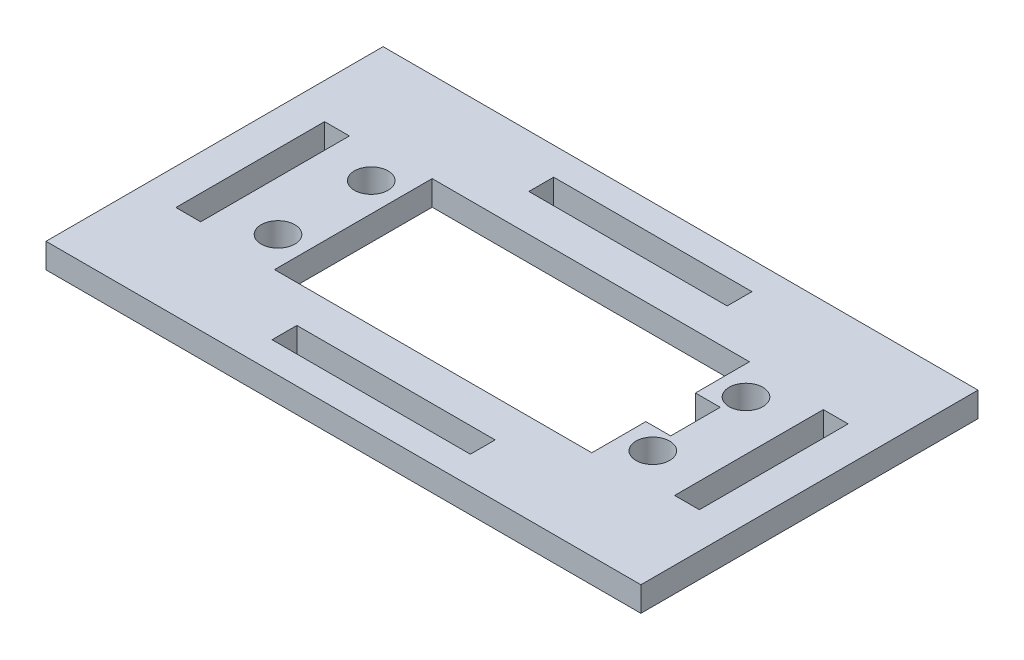
SolidWorks part; units mm, degrees
ref_plane "Front" through (0, 0, 0) normal (0, 0, 1) x (1, 0, 0)
ref_plane "Top" through (0, 0, 0) normal (0, 1, 0) x (1, 0, 0)
ref_plane "Right" through (0, 0, 0) normal (1, 0, 0) x (0, 0, -1)
sketch "Sketch1" plane through (0, 0, 0) normal (0, 1, 0) x (1, 0, 0)
  line L0 (0, 10.0965) -> (40.64, 10.0965) construction
  line L1 (0, 0) -> (40.64, 0)
  line L2 (0, 0) -> (0, 20.193)
  line L3 (0, 20.193) -> (40.64, 20.193)
  line L4 (40.64, 0) -> (40.64, 20.193)
  line L5 (-17.78, -11.4935) -> (58.42, -11.4935)
  line L6 (-17.78, -11.4935) -> (-17.78, 31.6865)
  line L7 (-17.78, 31.6865) -> (58.42, 31.6865)
  line L8 (58.42, -11.4935) -> (58.42, 31.6865)
  line L9 (44.323, 16.0655) -> (44.323, 4.1275) construction
  line L10 (20.32, 20.193) -> (20.32, 0) construction
  line L11 (7.62, -7.9375) -> (33.02, -7.9375)
  line L12 (7.62, 24.9555) -> (33.02, 24.9555)
  line L13 (7.62, 24.9555) -> (7.62, 28.1305)
  line L14 (7.62, 28.1305) -> (33.02, 28.1305)
  line L15 (33.02, 24.9555) -> (33.02, 28.1305)
  line L16 (-13.208, 19.6215) -> (-10.033, 19.6215)
  line L17 (-13.208, 19.6215) -> (-13.208, 0.5715)
  line L18 (-13.208, 0.5715) -> (-10.033, 0.5715)
  line L19 (-10.033, 19.6215) -> (-10.033, 0.5715)
  line L20 (33.02, -4.7625) -> (33.02, -7.9375)
  line L21 (7.62, -4.7625) -> (33.02, -4.7625)
  line L22 (7.62, -4.7625) -> (7.62, -7.9375)
  line L23 (53.848, 0.5715) -> (50.673, 0.5715)
  line L24 (50.673, 19.6215) -> (50.673, 0.5715)
  line L25 (53.848, 19.6215) -> (50.673, 19.6215)
  line L26 (53.848, 19.6215) -> (53.848, 0.5715)
  circle A0 centre (44.323, 16.0655) radius 2.159
  circle A1 centre (44.323, 4.1275) radius 2.159
  circle A2 centre (-3.683, 4.1275) radius 2.159
  circle A3 centre (-3.683, 16.0655) radius 2.159
  point P12 (20.32, 31.6865)
  point P14 (-17.78, 10.0965)
  point P19 (44.323, 10.0965)
  point P20 (20.32, 28.1305)
  point P22 (7.62, 26.543)
  point P35 (-10.033, 10.0965)
  point P36 (-11.6205, 0.5715)
  dimension "D5" = 4.318
  dimension "D1" = 20.193
  dimension "D2" = 40.64
  dimension "D3" = 76.2
  dimension "D4" = 43.18
  dimension "D6" = 4.1275
  dimension "D7" = 3.683
  dimension "D8" = 3.175
  dimension "D9" = 25.4
  dimension "D10" = 6.35
  dimension "D11" = 3.175
  dimension "D12" = 19.05
  dimension "D13" = 7.9375
extrude "Boss-Extrude1" add sketch "Sketch1" along normal blind 3.175
sketch "Sketch2" plane through (0, 3.175, 0) normal (0, 1, 0) x (1, 0, 0)
  line L0 (40.64, 0) -> (40.64, 20.193) construction
  line L1 (40.64, 13.2715) -> (43.815, 13.2715)
  line L2 (40.64, 13.2715) -> (40.64, 6.9215)
  line L3 (40.64, 6.9215) -> (43.815, 6.9215)
  line L4 (43.815, 13.2715) -> (43.815, 6.9215)
  point P6 (40.64, 10.0965)
  point P7 (43.815, 10.0965)
  dimension "D1" = 6.35
  dimension "D2" = 3.175
extrude "Cut-Extrude1" cut sketch "Sketch2" against normal up to surface (3.175 mm away) up to face at (-3.683, 0, -6.2865)
sketch "Sketch3" [suppressed] plane through (0, 3.175, 0) normal (0, 1, 0) x (1, 0, 0)
  line L0 (-10.033, 0.5715) -> (-10.033, 19.6215) construction
  line L1 (-10.033, 20.193) -> (50.673, 20.193)
  line L2 (-10.033, 20.193) -> (-10.033, 0)
  line L3 (-10.033, 0) -> (50.673, 0)
  line L4 (50.673, 20.193) -> (50.673, 0)
  line L5 (50.673, 19.6215) -> (50.673, 0.5715) construction
  line L6 (0, 0) -> (40.64, 0) construction
  line L7 (40.64, 20.193) -> (0, 20.193) construction
extrude "Boss-Extrude2" [suppressed] add sketch "Sketch3" against normal up to surface (3.175 mm away) up to face at (31.2738, 0, -10.0965)
sketch "Sketch4" [suppressed] plane through (0, 3.175, 0) normal (0, 1, 0) x (1, 0, 0)
  line L0 (58.42, -11.4935) -> (58.42, 31.6865) construction
  line L1 (-17.78, -11.4935) -> (58.42, -11.4935) construction
  line L2 (58.42, 10.0965) -> (-17.78, 10.0965) construction
  line L3 (-17.78, 31.6865) -> (-17.78, -11.4935) construction
  line L5 (58.42, 31.6865) -> (-17.78, 31.6865) construction
  line L6 (20.32, 31.6865) -> (20.32, -11.4935) construction
  circle A0 centre (45.72, -5.1435) radius 2.0193
  circle A1 centre (-5.08, -5.1435) radius 2.0193
  circle A2 centre (-5.08, 25.3365) radius 2.0193
  circle A3 centre (45.72, 25.3365) radius 2.0193
  dimension "D3" = 4.0386
  dimension "D1" = 12.7
  dimension "D2" = 6.35
extrude "Cut-Extrude2" [suppressed] cut sketch "Sketch4" against normal up to surface (3.175 mm away) up to face at (31.2738, 0, -10.0965)
